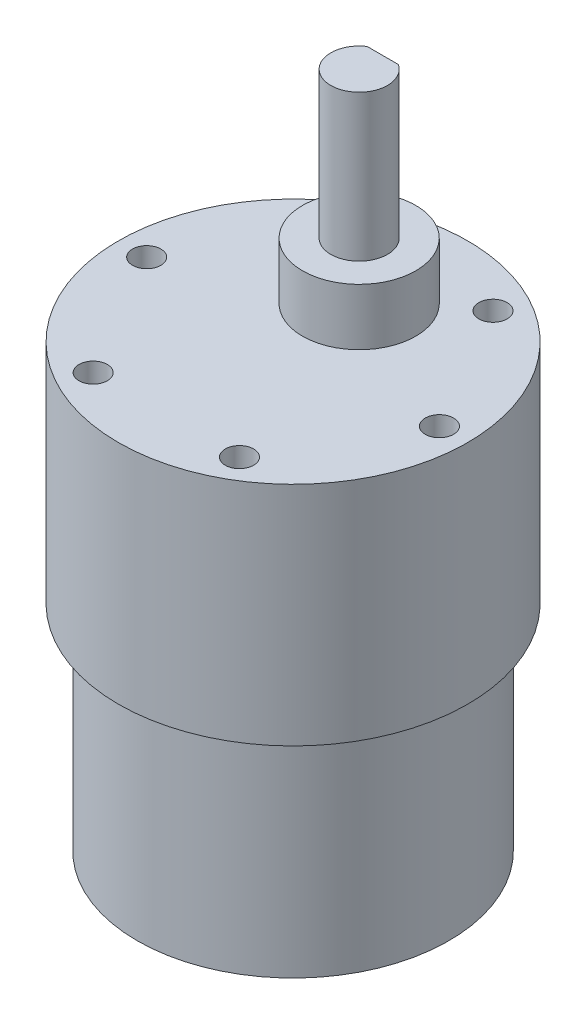
SolidWorks part; units mm, degrees
other "细节项目1"
ref_plane "前视" through (0, 0, 0) normal (0, 0, 1) x (1, 0, 0)
ref_plane "上视" through (0, 0, 0) normal (0, 1, 0) x (1, 0, 0)
ref_plane "右视" through (0, 0, 0) normal (1, 0, 0) x (0, 0, -1)
sketch "草图1" plane through (0, 0, 0) normal (0, 1, 0) x (1, 0, 0)
  circle A0 centre (0, 0) radius 16.5
  dimension "D1" = 33
extrude "凸台-拉伸1" add sketch "草图1" along normal blind 22.7
sketch "草图2" plane through (0, 22.7, 0) normal (0, 1, 0) x (1, 0, 0)
  circle A0 centre (0, 0) radius 18.5
  dimension "D1" = 37
extrude "凸台-拉伸2" add sketch "草图2" along normal blind 24
sketch "草图3" plane through (0, 46.7, 0) normal (0, 1, 0) x (1, 0, 0)
  circle A0 centre (0, 7) radius 6
  point P5 (0, 0)
  dimension "D1" = 12
  dimension "D2" = 7
extrude "凸台-拉伸3" add sketch "草图3" along normal blind 6
sketch "草图4" plane through (0, 52.7, 0) normal (0, 1, 0) x (1, 0, 0)
  circle A0 centre (0, 7) radius 3
  dimension "D1" = 6
extrude "凸台-拉伸4" add sketch "草图4" along normal blind 15.5
sketch "草图5" plane through (0, 68.2, 0) normal (0, 1, 0) x (1, 0, 0)
  line L0 (-1.6583, 9.5) -> (1.6583, 9.5)
  circle A0 centre (0, 7) radius 3
  circle M1 centre (0, 7) radius 3
  dimension "D2" = 6
  dimension "D1" = 2.5
extrude "切除-拉伸1" cut sketch "草图5" against normal blind 12 contours L0 M1 region at (0, 68.2, -9.7015)
sketch "草图6" plane through (0, 46.7, 0) normal (0, 1, 0) x (1, 0, 0)
  circle A0 centre (0, 0) radius 15.5 construction
  circle A1 centre (15.5, 0) radius 1.5
  circle A2 centre (7.75, -13.4234) radius 1.5
  circle A3 centre (-7.75, -13.4234) radius 1.5
  circle A4 centre (-15.5, 0) radius 1.5
  circle A5 centre (-7.75, 13.4234) radius 1.5
  circle A6 centre (7.75, 13.4234) radius 1.5
  point P17 (0, 0)
  dimension "D1" = 31
  dimension "D2" = 3
  dimension "D3" = 6
extrude "切除-拉伸2" cut sketch "草图6" against normal blind 10
cosmetic thread "装饰螺纹线1" parameters "D2"=3.5
cosmetic thread "装饰螺纹线2" parameters "D2"=3.5
cosmetic thread "装饰螺纹线3" parameters "D2"=3.5
cosmetic thread "装饰螺纹线4" parameters "D2"=3.5
cosmetic thread "装饰螺纹线5" parameters "D2"=3.5
cosmetic thread "装饰螺纹线6" parameters "D2"=3.5
sketch "草图7" plane through (0, 0, 0) normal (0, -1, 0) x (1, 0, 0)
  circle A0 centre (0, 0) radius 5
  dimension "D1" = 10
extrude "凸台-拉伸5" add sketch "草图7" along normal blind 2
fillet "圆角1" radius 0.5 1 edges at (0, -2, -5)
